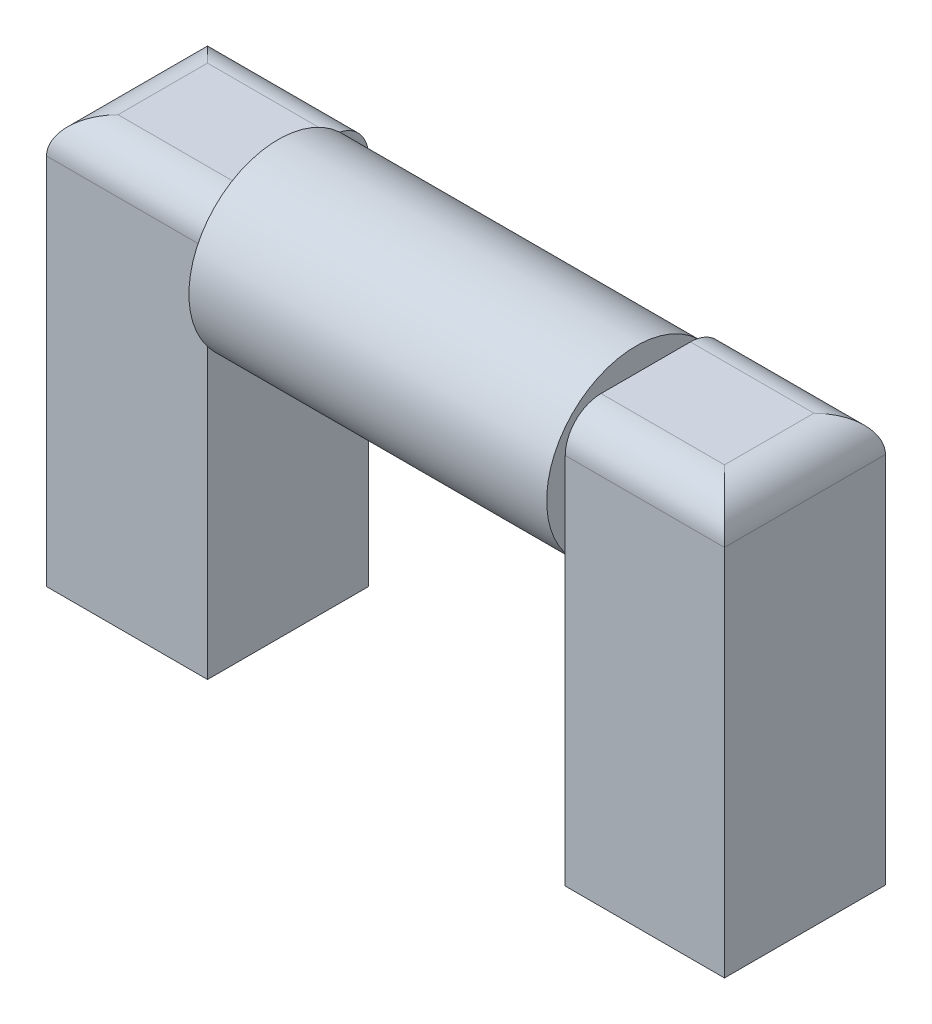
SolidWorks part; units mm, degrees
ref_plane "Ebene vorne" through (0, 0, 0) normal (0, 0, 1) x (1, 0, 0)
ref_plane "Ebene oben" through (0, 0, 0) normal (0, 1, 0) x (1, 0, 0)
ref_plane "Ebene rechts" through (0, 0, 0) normal (1, 0, 0) x (0, 0, -1)
sketch "Skizze1" plane through (0, 0, 0) normal (0, 0, 1) x (1, 0, 0)
  line L0 (0, 0) -> (-4.5, 0)
  line L1 (-4.5, 0) -> (-4.5, 11.4233)
  line L2 (-4.5, 11.4233) -> (0, 11.4233)
  line L3 (0, 11.4233) -> (0, 0)
  line L4 (10, 0) -> (14.4514, 0)
  line L5 (14.4514, 0) -> (14.4514, 11.4233)
  line L6 (14.4514, 11.4233) -> (10, 11.4233)
  line L7 (10, 11.4233) -> (10, 0)
  dimension "D1" = 10
  dimension "D2" = 4.5
  dimension "D3" = 11.4233
  dimension "D4" = 11.4233
  dimension "D5" = 4.4514
extrude "Aufsatz-Linear austragen1" add sketch "Skizze1" along normal blind 4.5
sketch "Skizze2" plane through (0, 0, 0) normal (1, 0, 0) x (0, 0, -1)
  circle A0 centre (-2.5203, 9.5865) radius 2.5
extrude "Aufsatz-Linear austragen2" add sketch "Skizze2" along normal blind 10
fillet "Verrundung4" radius 1 6 edges at (-2.25, 11.4233, 4.5) (-4.5, 11.4233, 2.25) (-2.25, 11.4233, 0) (12.2257, 11.4233, 4.5) (14.4514, 11.4233, 2.25) (12.2257, 11.4233, 0)
